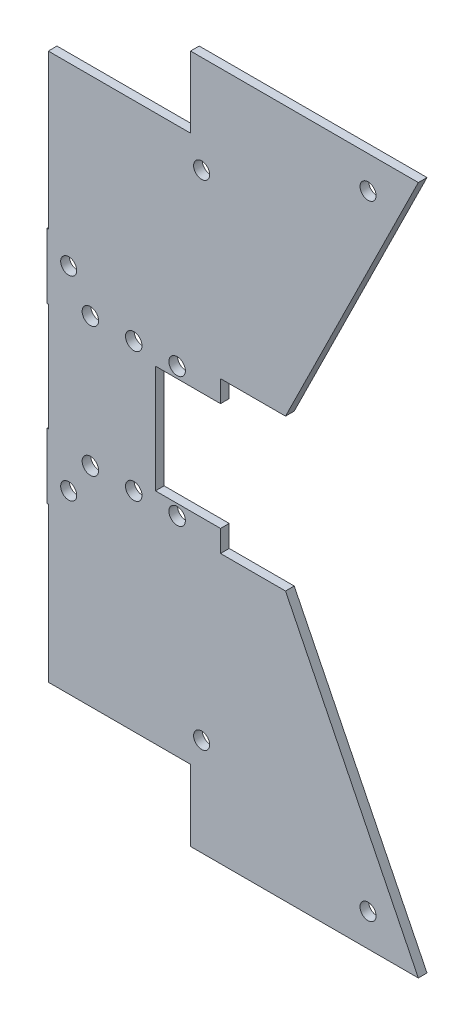
SolidWorks part; units mm, degrees
material "Thornel Mat VMA"
ref_plane "Front Plane" through (0, 0, 0) normal (0, 0, 1) x (1, 0, 0)
ref_plane "Top Plane" through (0, 0, 0) normal (0, 1, 0) x (1, 0, 0)
ref_plane "Right Plane" through (0, 0, 0) normal (1, 0, 0) x (0, 0, -1)
sketch "Sketch1" plane through (0, 0, 0) normal (0, 0, 1) x (1, 0, 0)
  line L0 (-2.9301, -104.5098) -> (-3.3149, -104.5098)
  line L1 (-3.3149, -72.8868) -> (-2.9301, -72.8868)
  line L78 (47.4851, -66.5368) -> (47.4851, -72.8868)
  line L79 (47.4851, -104.5098) -> (47.4851, -110.8598)
  line L80 (66.5174, -66.5368) -> (105.3971, 12.1397)
  line L81 (105.3971, 12.1397) -> (38.7094, 12.1397)
  line L88 (38.7094, 12.1397) -> (38.7094, -8.6883)
  line L89 (-2.9301, -8.6883) -> (38.7094, -8.6883)
  line L90 (-3.3149, -53.8368) -> (-2.9301, -53.8368)
  line L91 (-2.9301, -53.8368) -> (-2.9301, -8.6883)
  line L92 (-3.3149, -66.5368) -> (-3.3149, -53.8368)
  line L93 (-3.3149, -72.8868) -> (-3.3149, -66.5368)
  line L94 (-2.9301, -104.5098) -> (-2.9301, -72.8868)
  line L95 (-3.3149, -110.8598) -> (-3.3149, -104.5098)
  line L96 (66.5174, -110.8598) -> (105.3971, -189.5363)
  line L97 (105.3971, -189.5363) -> (38.7094, -189.5363)
  line L98 (38.7094, -189.5363) -> (38.7094, -168.7083)
  line L99 (-2.9301, -168.7083) -> (38.7094, -168.7083)
  line L106 (-3.3149, -110.8598) -> (-3.3149, -123.5598)
  line L107 (-3.3149, -123.5598) -> (-2.9301, -123.5598)
  line L108 (66.5174, -110.8598) -> (47.4851, -110.8598)
  line L109 (47.4851, -66.5368) -> (66.5174, -66.5368)
  line L110 (47.4851, -104.5098) -> (47.4851, -72.8868)
  line L111 (-2.9301, -123.5598) -> (-2.9301, -168.7083)
  circle A0 centre (90.6739, 2.6147) radius 2.3495
  circle A1 centre (41.9566, -16.4353) radius 2.3495
  circle A2 centre (3.0351, -60.1868) radius 2.3495
  circle A3 centre (3.0351, -117.2098) radius 2.3495
  circle A4 centre (41.9566, -160.9613) radius 2.3495
  circle A5 centre (90.6739, -180.0113) radius 2.3495
  point P2 (90.6739, 2.6147)
  point P4 (41.9566, -16.4353)
  point P6 (3.0351, -60.1868)
  point P8 (3.0351, -117.2098)
  point P10 (41.9566, -160.9613)
  point P11 (90.6739, -180.0113)
  dimension "D2" = 4.699
  dimension "D1" = 66.6876
extrude "Boss-Extrude1" add sketch "Sketch1" along normal blind 2.54
sketch "Sketch2" plane through (0, 0, 2.54) normal (0, 0, 1) x (1, 0, 0)
  line L0 (-3.3149, -53.8368) -> (-3.3149, -72.8868) construction
  line L1 (47.4851, -66.5368) -> (66.5174, -66.5368) construction
  line L2 (47.4851, -88.6983) -> (-2.9301, -88.6983) construction
  line L3 (47.4851, -110.8598) -> (47.4851, -66.5368) construction
  line L4 (-2.9301, -72.8868) -> (-2.9301, -104.5098) construction
  circle A0 centre (9.3851, -69.7118) radius 2.413
  circle A1 centre (22.0851, -69.7118) radius 2.413
  circle A2 centre (34.7851, -69.7118) radius 2.413
  circle A4 centre (34.7851, -107.6848) radius 2.413
  circle A5 centre (22.0851, -107.6848) radius 2.413
  circle A6 centre (9.3851, -107.6848) radius 2.413
  dimension "D1" = 4.826
  dimension "D2" = 4.826
  dimension "D3" = 4.826
  dimension "D4" = 12.7
  dimension "D5" = 12.7
  dimension "D6" = 12.7
  dimension "D7" = 3.175
  dimension "D8" = 0
  dimension "D9" = 0
extrude "Cut-Extrude1" cut sketch "Sketch2" against normal through all
sketch "Sketch3" plane through (0, 0, 2.54) normal (0, 0, 1) x (1, 0, 0)
  line L0 (47.4851, -110.8598) -> (47.4851, -66.5368) construction
  line L1 (47.4851, -72.8868) -> (28.4351, -72.8868)
  line L2 (47.4851, -72.8868) -> (47.4851, -104.5098)
  line L3 (47.4851, -104.5098) -> (28.4351, -104.5098)
  line L4 (28.4351, -72.8868) -> (28.4351, -104.5098)
  line L5 (47.4851, -66.5368) -> (66.5174, -66.5368) construction
  line L6 (66.5174, -110.8598) -> (47.4851, -110.8598) construction
  circle A0 centre (22.0851, -69.7118) radius 2.413 construction
  dimension "D3" = 6.35
  dimension "D1" = 6.35
  dimension "D2" = 6.35
extrude "Cut-Extrude2" cut sketch "Sketch3" against normal through all
